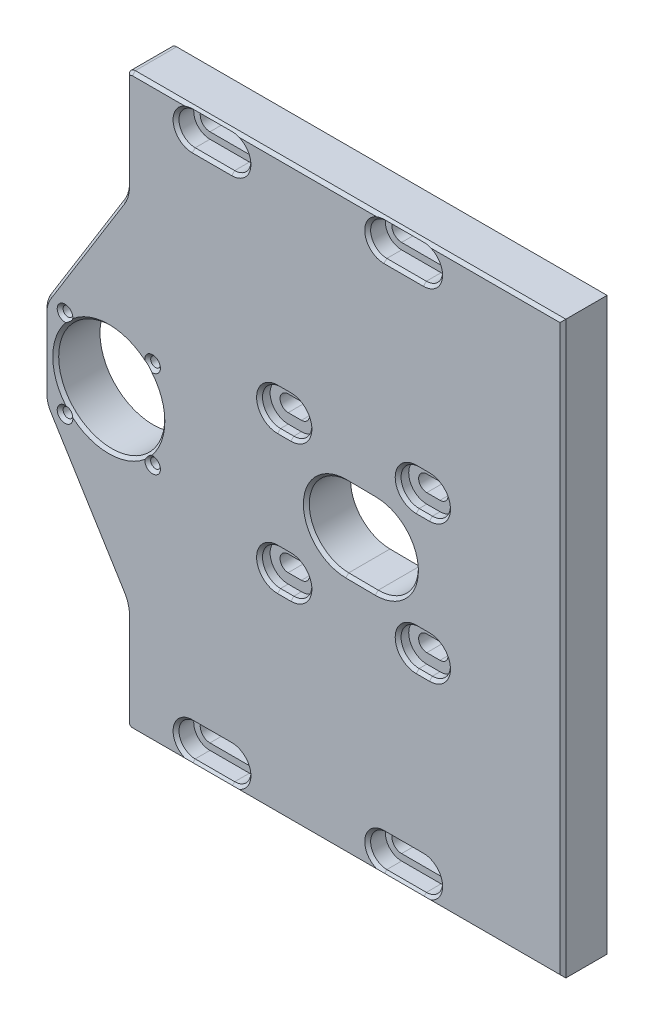
SolidWorks part; units mm, degrees
ref_plane "Front Plane" through (0, 0, 0) normal (0, 0, 1) x (1, 0, 0)
ref_plane "Top Plane" through (0, 0, 0) normal (0, 1, 0) x (1, 0, 0)
ref_plane "Right Plane" through (0, 0, 0) normal (1, 0, 0) x (0, 0, -1)
sketch "Sketch1" plane through (0, 0, 0) normal (0, 0, 1) x (1, 0, 0)
  line L6 (-12, 227) -> (0, 227)
  line L24 (-148, 255) -> (-148, 190) construction
  line L31 (-148, 70) -> (-148, 10) construction
  line L32 (-148, 33.5) -> (-12, 33.5) construction
  line L34 (0, 227) -> (0, 33.5)
  line L36 (-12, 227) -> (-148, 227) construction
  line L37 (-148, 227) -> (-148, 190)
  line L38 (-148, 70) -> (-148, 33.5)
  line L39 (-148, 33.5) -> (-12, 33.5)
  line L43 (-12, 227) -> (-148, 227)
  line L45 (-176, 115.2267) -> (-176, 144.7733)
  line L46 (-176, 144.7733) -> (-148, 190)
  line L47 (-176, 115.2267) -> (-148, 70)
  line L52 (0, 33.5) -> (-12, 33.5)
  circle A10 centre (-154, 130) radius 18
extrude "Boss-Extrude1" add sketch "Sketch1" along normal blind 15
sketch "Sketch2" plane through (0, 0, 15) normal (0, 0, 1) x (1, 0, 0)
  circle A1 centre (-139.1508, 115.1508) radius 2.25
  circle A3 centre (-168.8492, 115.1508) radius 2.25
  circle A5 centre (-168.8492, 144.8492) radius 2.25
  circle A7 centre (-139.1508, 144.8492) radius 2.25
hole_wizard "M4x0.7 Tapped Hole1" positions "Sketch3" profile "Sketch4" tap size "M4x0.7" standard "ANSI Metric"
sketch "Sketch3" plane through (0, 0, 15) normal (0, 0, 1) x (1, 0, 0)
  point P0 (-168.8492, 144.8492)
  point P3 (-139.1508, 144.8492)
  point P6 (-139.1508, 115.1508)
  point P9 (-168.8492, 115.1508)
sketch "Sketch4" plane through (-168.8492, 144.8492, 15) normal (1, 0, 0) x (0, -1, 0)
  line L0 (0, 0) -> (0, 20)
  line L1 (0, 20) -> (1.65, 19.0086)
  line L2 (1.65, 19.0086) -> (1.65, 0)
  line L5 (1.65, 0) -> (0, 0)
  line L10 (0, 20) -> (-1.65, 19.0086) construction
  line L11 (0, -6.35) -> (0, 107.95) construction
  dimension "Tap Drill Dia." = 3.3
  dimension "Tap Drill Depth" = 20
  dimension "Drill Angle" = 118
cosmetic thread "Hole Thread1" parameters "D1"=12, "D2"=4
cosmetic thread "Hole Thread2" parameters "D1"=12, "D2"=4
cosmetic thread "Hole Thread7" parameters "D1"=12, "D2"=4
cosmetic thread "Hole Thread8" parameters "D1"=12, "D2"=4
hole_wizard "CBORE SLOT for M6 SHCS1" positions "Sketch5" profile "Sketch6" size "M6" standard "ANSI Metric" slot yes
sketch "Sketch5" plane through (0, 0, 15) normal (0, 0, 1) x (1, 0, 0)
  line L0 (-64, 220) -> (-44, 220) construction
  point P0 (-54, 220)
  point P3 (-119, 220)
  point P6 (-54, 40.5)
  point P9 (-119, 40.5)
  dimension "D1" = 20
sketch "Sketch6" plane through (-54, 220, 15) normal (1, 0, 0) x (0, -1, 0)
  line L0 (0, 0) -> (0, 29.9828)
  line L1 (0, 29.9828) -> (3.3, 28)
  line L2 (3.3, 28) -> (3.3, 6)
  line L3 (3.3, 6) -> (5.5, 6)
  line L4 (5.5, 6) -> (5.5, 0)
  line L5 (5.5, 0) -> (0, 0)
  line L10 (0, 29.9828) -> (-3.3, 28) construction
  line L11 (0, -6.35) -> (0, 107.95) construction
  dimension "Hole Dia." = 6.6
  dimension "Hole Depth" = 28
  dimension "C'Bore Dia." = 11
  dimension "C'Bore Depth" = 6
  dimension "Drill Angle" = 118
sketch "Sketch7" plane through (0, 0, 15) normal (0, 0, 1) x (1, 0, 0)
  line L0 (-73.5, 129.1439) -> (-88.5, 129.1439)
  line L1 (-89.5, 152.6439) -> (-94.5, 152.6439)
  line L2 (-42.5, 152.6439) -> (-47.5, 152.6439)
  line L3 (-42.5, 105.6439) -> (-47.5, 105.6439)
  line L4 (-89.5, 105.6439) -> (-94.5, 105.6439)
  circle A1 centre (-50, 105.6439) radius 2.85 construction
  circle A2 centre (-73.5, 129.1439) radius 13.5
  circle A3 centre (-73.5, 129.1439) radius 13.5
  circle A4 centre (-97, 105.6439) radius 2.85 construction
  circle A5 centre (-97, 152.6439) radius 2.85 construction
  circle A6 centre (-50, 152.6439) radius 2.85 construction
  circle A7 centre (-50, 105.6439) radius 2.85
  circle A8 centre (-97, 105.6439) radius 2.85
  circle A9 centre (-97, 152.6439) radius 2.85
  circle A10 centre (-50, 152.6439) radius 2.85
  dimension "D1" = 1
hole_wizard "Ø1.0mm Dowel Slot1" positions "Sketch8" profile "Sketch9" size "Ø1.0" standard "ANSI Metric" slot yes
sketch "Sketch8" plane through (0, 0, 15) normal (0, 0, 1) x (1, 0, 0)
  line L0 (-86.9991, 129.3233) -> (-50.0009, 128.9645) construction
  point P0 (-68.5, 129.1439)
  dimension "D1" = 37
sketch "Sketch9" plane through (-68.5, 129.1439, 15) normal (1, 0, 0) x (0, -1, 0)
  line L0 (0, 0) -> (0, 36.1116)
  line L1 (0, 36.1116) -> (13.5, 28)
  line L2 (13.5, 28) -> (13.5, 0)
  line L5 (13.5, 0) -> (0, 0)
  line L10 (0, 36.1116) -> (-13.5, 28) construction
  line L11 (0, -6.35) -> (0, 107.95) construction
  dimension "Hole Dia." = 27
  dimension "Hole Depth" = 28
  dimension "Drill Angle" = 118
hole_wizard "CBORE SLOT for M5 Hex Head Bolt1" positions "Sketch10" profile "Sketch11" size "M5" standard "ANSI Metric" slot yes
sketch "Sketch10" plane through (0, 0, 15) normal (0, 0, 1) x (1, 0, 0)
  line L0 (-99.5, 152.6439) -> (-89.5, 152.6439) construction
  point P0 (-94.5, 152.6439)
  point P5 (-94.5, 105.6439)
  point P8 (-47.5, 152.6439)
  point P11 (-47.5, 105.6439)
  dimension "D1" = 10
sketch "Sketch11" plane through (-94.5, 152.6439, 15) normal (1, 0, 0) x (0, -1, 0)
  line L0 (0, 0) -> (0, 29.6524)
  line L1 (0, 29.6524) -> (2.75, 28)
  line L2 (2.75, 28) -> (2.75, 3.58)
  line L3 (2.75, 3.58) -> (6.12, 3.58)
  line L4 (6.12, 3.58) -> (6.12, 0)
  line L5 (6.12, 0) -> (0, 0)
  line L10 (0, 29.6524) -> (-2.75, 28) construction
  line L11 (0, -6.35) -> (0, 107.95) construction
  dimension "Hole Dia." = 5.5
  dimension "Hole Depth" = 28
  dimension "C'Bore Dia." = 12.24
  dimension "C'Bore Depth" = 3.58
  dimension "Drill Angle" = 118
fillet "Fillet1" radius 10 4 edges at (-148, 70, 7.5) (-176, 115.2267, 7.5) (-176, 144.7733, 7.5) (-148, 190, 7.5)
fillet "Fillet2" radius 2 2 edges at (-148, 33.5, 7.5) (-148, 227, 7.5)
chamfer "Chamfer1" distance 1 angle 45 55 edges at (-148.3817, 69.8914, 15) (-162, 92.6134, 15) (-175.6183, 115.3353, 15) (-176, 130, 15) (-175.6183, 144.6647, 15) (-162, 167.3866, 15) (-148.3817, 190.1086, 15) (-148, 208.9225, 15) (-147.4142, 226.4142, 15) (-73, 227, 15) (-73, 33.5, 15) (-147.4142, 34.0858, 15) (-148, 51.3275, 15) (-167.1992, 115.1508, 15) (-137.5008, 115.1508, 15) (-137.5008, 144.8492, 15) (-167.1992, 144.8492, 15) (-86.9991, 129.3233, 15) (-68.6309, 115.6445, 15) (-50.0009, 128.9645, 15) (-68.3691, 142.6433, 15) (-55.87, 105.6439, 15) (-47.5, 99.5239, 15) (-39.13, 105.6439, 15) (-47.5, 111.7639, 15) (-47.5, 146.5239, 15) (-39.13, 152.6439, 15) (-47.5, 158.7639, 15) (-55.87, 152.6439, 15) (-94.5, 99.5239, 15) (-86.13, 105.6439, 15) (-94.5, 111.7639, 15) (-102.87, 105.6439, 15) (-102.87, 152.6439, 15) (-94.5, 146.5239, 15) (-86.13, 152.6439, 15) (-94.5, 158.7639, 15) (0, 130.25, 15) (-119, 35, 15) (-106.8, 40.5, 15) (-119, 46, 15) (-131.2, 40.5, 15) (-41.8, 40.5, 15) (-54, 46, 15) (-66.2, 40.5, 15) (-54, 35, 15) (-119, 225.5, 15) (-131.2, 220, 15) (-119, 214.5, 15) (-106.8, 220, 15) (-54, 225.5, 15) (-66.2, 220, 15) (-54, 214.5, 15) (-41.8, 220, 15) (-136, 130, 15)
sketch "Sketch12" plane through (0, 0, 0) normal (0, 0, -1) x (-1, 0, 0)
  circle A0 centre (154, 151.5) radius 3.5 construction
  circle A1 centre (154, 151.5) radius 3.5
